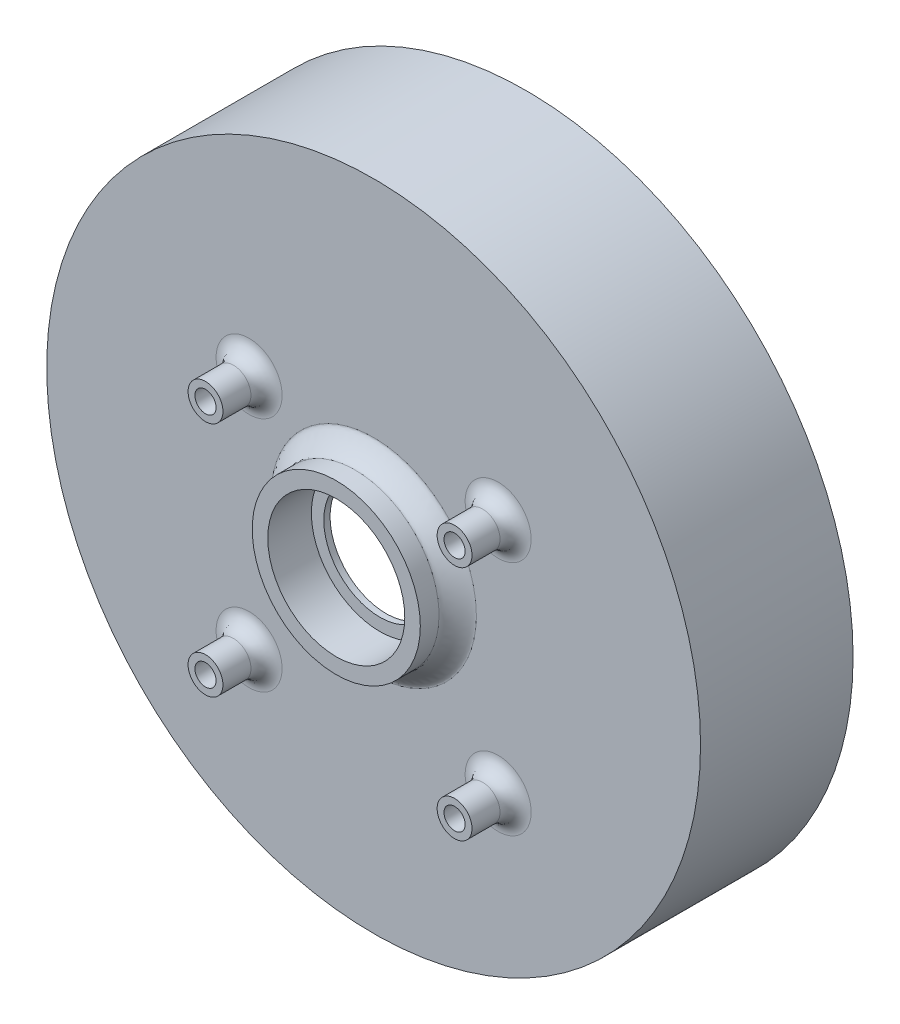
SolidWorks part; units mm, degrees
ref_plane "Front Plane" through (0, 0, 0) normal (0, 0, 1) x (1, 0, 0)
ref_plane "Top Plane" through (0, 0, 0) normal (0, 1, 0) x (1, 0, 0)
ref_plane "Right Plane" through (0, 0, 0) normal (1, 0, 0) x (0, 0, -1)
sketch "Sketch1" plane through (0, 0, 0) normal (0, 0, 1) x (1, 0, 0)
  circle A0 centre (0, 0) radius 45
  circle A1 centre (0, 0) radius 52.5
  circle A2 centre (0, 0) radius 11
  dimension "D1" = 90
  dimension "D2" = 105
  dimension "D3" = 22
extrude "Boss-Extrude1" add sketch "Sketch1" along normal blind 22.5 contours A1 A0 region at (-51.0151, 0, 0)
sketch "Sketch2" plane through (0, 0, 0) normal (0, 0, 1) x (1, 0, 0)
  line L0 (-20, 15) -> (20, 15) construction
  line L1 (-20, -23) -> (20, -23) construction
  line L2 (-20, 18) -> (20, 18)
  line L3 (-16, -35) -> (16, -35)
  line L4 (-23, 15) -> (-23, -23)
  line L5 (23, 15) -> (23, -23)
  line L6 (-27.3518, -23) -> (-27.3518, -29) construction
  line L7 (-27.3518, -29) -> (-27.3518, -35) construction
  line L8 (-27.3518, -29) -> (32.2638, -29) construction
  line L9 (-27.3518, -35) -> (32.2638, -35) construction
  line L10 (-16, -35) -> (-16, -29)
  line L11 (16, -35) -> (16, -29)
  line L12 (-20.8734, -26.0636) -> (-17.0471, -27.4916)
  line L13 (0, 21.7483) -> (0, -55.2269) construction
  line L15 (20.8734, -26.0636) -> (17.0471, -27.4916)
  circle A0 centre (0, 0) radius 3.2
  circle A1 centre (20, 15) radius 1.25
  circle A2 centre (-20, 15) radius 1.25
  circle A3 centre (-20, -23) radius 1.25
  circle A4 centre (20, -23) radius 1.25
  arc A5 (-20, 18) -> (-23, 15) centre (-20, 15) ccw
  arc A6 (23, 15) -> (20, 18) centre (20, 15) ccw
  arc A8 (-16, -29) -> (-17.0471, -27.4916) centre (-17.61, -29) ccw
  arc A9 (16, -29) -> (17.0471, -27.4916) centre (17.61, -29) cw
  arc A11 (-23, -23) -> (-20.8734, -26.0636) centre (-19.73, -23) ccw
  arc A12 (23, -23) -> (20.8734, -26.0636) centre (19.73, -23) cw
  point P5 (0, 15)
  point P10 (0, -23)
  point P18 (0, -35)
  dimension "D1" = 15
  dimension "D3" = 2.5
  dimension "D4" = 2.5
  dimension "D7" = 2.5
  dimension "D8" = 2.5
  dimension "D11" = 6
  dimension "D9" = 6
  dimension "D12" = 6.4
  dimension "D15" = 3.27
  dimension "D16" = 1.61
  dimension "D2" = 40
  dimension "D5" = 40
  dimension "D6" = 23
  dimension "D10" = 32
  dimension "D13" = 6
  dimension "D14" = 6
  dimension "D17" = 7.3518
extrude "Boss-Extrude2" add sketch "Sketch1<2>" along normal blind 2 from surface contours A1 A0 | A0 region at (-43.7272, 0, 0) region at (-51.0151, 0, 0) starting at face at (45, 0, 22.5)
sketch "Sketch1<2>" plane through (0, 0, 0) normal (0, 0, 1) x (1, 0, 0) same geometry as "Sketch1"
sketch "Sketch3" plane through (0, 0, 24.5) normal (0, 0, 1) x (1, 0, 0)
  circle A0 centre (-20, -23) radius 1.25 construction
  circle A1 centre (20, -23) radius 1.25 construction
  circle A2 centre (20, 15) radius 1.25 construction
  circle A3 centre (-20, 15) radius 1.25 construction
  circle A4 centre (-20, -23) radius 1.25 construction
  circle A5 centre (20, -23) radius 1.25 construction
  circle A6 centre (20, 15) radius 1.25 construction
  circle A7 centre (-20, 15) radius 1.25 construction
  circle A8 centre (-20, 15) radius 1.7
  circle A9 centre (20, 15) radius 1.7
  circle A10 centre (20, -23) radius 1.7
  circle A11 centre (-20, -23) radius 1.7
  circle A12 centre (-20, 15) radius 2.8
  circle A13 centre (20, 15) radius 2.8
  circle A14 centre (20, -23) radius 2.8
  circle A15 centre (-20, -23) radius 2.8
  dimension "D1" = 3.4
  dimension "D2" = 5.6
extrude "Boss-Extrude3" add sketch "Sketch3" along normal blind 7
fillet "Fillet1" radius 2.5 4 edges at (-17.2, -23, 24.5) (22.8, -23, 24.5) (22.8, 15, 24.5) (-17.2, 15, 24.5) conic radius 2.5
sketch "Sketch4" plane through (0, 0, 24.5) normal (0, 0, 1) x (1, 0, 0)
  circle A0 centre (0, 0) radius 13.5
  circle A1 centre (0, 0) radius 11
  circle M7 centre (0, 0) radius 11
  dimension "D1" = 27
extrude "Boss-Extrude4" add sketch "Sketch4" along normal blind 6 contours A0 M7 region at (-13.1182, 0, 24.5)
sketch "Sketch5" plane through (0, 0, 22.5) normal (0, 0, -1) x (-1, 0, 0)
  circle A0 centre (0, 0) radius 9
  circle A1 centre (0, 0) radius 11
  dimension "D1" = 18
extrude "Boss-Extrude5" add sketch "Sketch5" against normal blind 1
sketch "Sketch7" plane through (0, 0, 0) normal (0, 0, -1) x (-1, 0, 0)
  circle A0 centre (0, 0) radius 48.75 construction
  circle A1 centre (-34.4715, 34.4715) radius 2.15
  circle A2 centre (34.4715, 34.4715) radius 2.15
  circle A3 centre (34.4715, -34.4715) radius 2.15
  circle A4 centre (-34.4715, -34.4715) radius 2.15
  point P5 (-64.2069, 0.643)
  point P6 (0, 0)
  point P7 (0, 48.75)
  point P14 (0, 0)
  point P15 (0, 0)
  point P16 (-34.3724, 34.5703)
  dimension "D1" = 97.5
  dimension "D2" = 4.3
  dimension "D3" = 4
extrude "Cut-Extrude1" cut sketch "Sketch7" against normal blind 10
sketch "Sketch8" plane through (0, 0, 0) normal (0, 1, 0) x (1, 0, 0)
  line L0 (0, -13.1345) -> (2.8495, -8.1989)
  line L1 (0, -13.1345) -> (-2.9097, -8.2342)
  arc A0 (2.8495, -8.1989) -> (-2.9097, -8.2342) centre (-0.0404, -6.5304) ccw
  dimension "D1" = 60
extrude "Cut-Extrude3" cut sketch "Sketch8" against normal blind 20 from offset 40 contours L0 A0 L1 region at (-0.0359, 0, 7.2656) offset against normal yes
fillet "Fillet2" radius 3 1 edges at (13.5, 0, 24.5) conic radius 10
